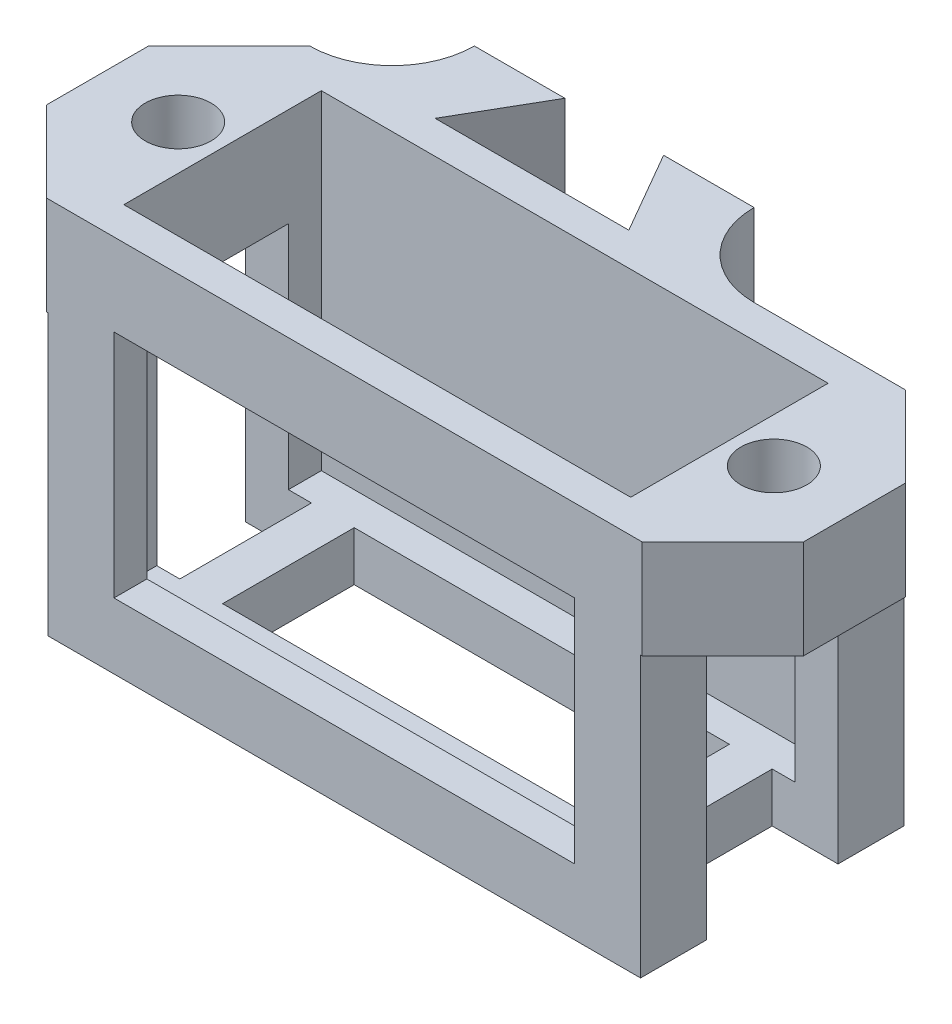
SolidWorks part; units mm, degrees
note: The reader was unsure of these and kept them because the rebuilt part matched: shared geometry of "Sketch3<3>", "Sketch2<3>".
ref_plane "Front Plane" through (0, 0, 0) normal (0, 0, 1) x (1, 0, 0)
ref_plane "Top Plane" through (0, 0, 0) normal (0, 1, 0) x (1, 0, 0)
ref_plane "Right Plane" through (0, 0, 0) normal (1, 0, 0) x (0, 0, -1)
sketch "Sketch1" plane through (0, 0, 0) normal (0, 0, 1) x (1, 0, 0)
  line L0 (-15, 15) -> (15, 15)
  line L1 (15, 15) -> (15, -15)
  line L2 (15, -15) -> (-15, -15)
  line L3 (-15, -15) -> (-15, 15)
  line L4 (-15, 0) -> (15, 0) construction
  line L5 (-15, 5) -> (-23, 5)
  line L6 (-23, 5) -> (-23, -1)
  line L7 (-23, -1) -> (-18, -1)
  line L8 (-18, -1) -> (-18, -18)
  line L9 (-18, -18) -> (18, -18)
  line L10 (18, -18) -> (18, -1)
  line L11 (18, -1) -> (23, -1)
  line L12 (23, -1) -> (23, 5)
  line L13 (23, 5) -> (15, 5)
  line L14 (-15, 5) -> (15, 5)
  point P6 (0, 0)
  dimension "D1" = 30
  dimension "D2" = 30
  dimension "D3" = 20
  dimension "D4" = 3
  dimension "D5" = 3
  dimension "D6" = 5
  dimension "D7" = 6
extrude "Extrude1" add sketch "Sketch1" along normal mid plane 16 contours L12 L13 L1 L2 L3 L5 L6 L7 L8 L9 L10 L11 | L4 L3 L2 L1 | L3 L4 L1 L14
sketch "Sketch2" plane through (0, 0, 0) normal (0, 1, 0) x (1, 0, 0)
  line L0 (-15.4, 0) -> (15.4, 0) construction
  line L1 (0, -6) -> (0, 6) construction
  line L2 (-15.4, -6) -> (-15.4, 6)
  line L3 (-15.4, 6) -> (15.4, 6)
  line L4 (15.4, 6) -> (15.4, -6)
  line L5 (15.4, -6) -> (-15.4, -6)
  line L6 (-18.1, 0) -> (-15.4, 0) construction
  line L7 (15.4, 0) -> (18.1, 0) construction
  line L8 (23, -3.1) -> (18.1, -8)
  line L9 (23, -8) -> (23, 8) construction
  line L11 (23, -8) -> (-23, -8) construction
  line L12 (18.1, -8) -> (23, -8)
  line L14 (23, -8) -> (23, -3.1)
  line L15 (18.1, 8) -> (23, 3.1)
  line L17 (23, 8) -> (-23, 8) construction
  line L18 (23, 3.1) -> (23, 8)
  line L20 (23, 8) -> (18.1, 8)
  line L21 (-18.1, 8) -> (-23, 3.1)
  line L22 (-23, -8) -> (-23, 8) construction
  line L23 (-23, 3.1) -> (-23, 8)
  line L24 (-23, 8) -> (-18.1, 8)
  line L25 (-23, -3.1) -> (-18.1, -8)
  line L26 (-18.1, -8) -> (-23, -8)
  line L27 (-23, -8) -> (-23, -3.1)
  line L28 (-11.4, 4) -> (11.4, 4)
  line L29 (-11.4, 4) -> (-11.4, -4)
  line L30 (-11.4, -4) -> (11.4, -4)
  line L31 (11.4, -4) -> (11.4, 4)
  circle A0 centre (-18.1, 0) radius 2
  circle A1 centre (18.1, 0) radius 2
  point P2 (0, 0)
  point P6 (0, 0)
  point P46 (-11.4, 0)
  point P47 (11.4, 0)
  dimension "D4" = 4
  dimension "D1" = 12
  dimension "D2" = 30.8
  dimension "D3" = 36.2
  dimension "D5" = 2
  dimension "D6" = 4
  dimension "D7" = 4
extrude "Extrude2" cut sketch "Sketch2" against normal blind 20 from surface at 5 contours L27 L26 L25 | A0 | L24 L23 L21 | L30 L31 L28 L29 | L5 L4 L3 L2 L31 L30 L29 L28 | L18 L20 L15 | A1 | L12 L14 L8 starting at face at (0, 5, 0)
sketch "Sketch3" plane through (0, 0, 0) normal (0, 0, 1) x (1, 0, 0)
  line L0 (-14, -14) -> (14, -14)
  line L1 (14, -14) -> (14, 0)
  line L2 (14, 0) -> (-14, 0)
  line L3 (-18, -1) -> (-14, -1)
  line L4 (-14, 0) -> (-14, -14)
  line L5 (-18, -18) -> (18, -18) construction
  line L6 (18, -18) -> (18, -1) construction
  line L7 (-18, -1) -> (-18, -18) construction
  line L8 (-15, 5) -> (15, 5) construction
  line L9 (18, -1) -> (14, -1)
  line L10 (-18, -1) -> (-18, -18) construction
  line L11 (-18, -1) -> (-18, -18)
  line L12 (-18, -18) -> (-14, -18)
  line L13 (-18, -18) -> (18, -18) construction
  line L14 (-14, -18) -> (-14, -14)
  line L17 (18, -1) -> (18, -18)
  line L18 (18, -18) -> (14, -18)
  line L19 (14, -18) -> (14, -14)
  dimension "D1" = 4
  dimension "D2" = 4
  dimension "D3" = 4
  dimension "D4" = 5
extrude "Extrude3" cut sketch "Sketch3" against normal up to surface (14 mm away) from surface at 8 contours L2 L4 L0 L1 up to face at (0, -5, -6) starting at face at (0, -3.75, 8)
extrude "Extrude4" cut sketch "Sketch3<3>" against normal mid plane 8
sketch "Sketch3<3>" plane through (0, 0, 0) normal (0, 0, 1) x (1, 0, 0) same geometry as "Sketch3"
extrude "Extrude5" cut sketch "Sketch2<3>" against normal up to surface (3 mm away) from surface at -15 contours L30 L31 L28 L29 up to face at (0, -18, 0) starting at face at (0, -15, 0)
sketch "Sketch2<3>" plane through (0, 0, 0) normal (0, 1, 0) x (1, 0, 0) same geometry as "Sketch2"
sketch "Sketch4" plane through (0, 0, 0) normal (0, 1, 0) x (1, 0, 0)
  line L0 (3.9, 8) -> (3.9, 13)
  line L1 (3.9, 13) -> (-1.6, 13)
  line L2 (-1.6, 13) -> (1.2868, 8)
  line L3 (18.1, 8) -> (-18.1, 8) construction
  line L4 (-13.1, 8) -> (-13.1, 13)
  line L5 (-13.1, 13) -> (-7.6, 13)
  line L6 (-7.6, 13) -> (-10.4868, 8)
  line L7 (-10.4868, 8) -> (-18.1, 8)
  line L8 (1.2868, 8) -> (8.9, 8)
  line L9 (18.1, 8) -> (-18.1, 8) construction
  line L10 (18.1, 8) -> (-18.1, 8) construction
  arc A0 (-13.1, 13) -> (-18.1, 8) centre (-18.1, 13) cw
  arc A1 (3.9, 13) -> (8.9, 8) centre (8.9, 13) ccw
  dimension "D1" = 5
  dimension "D2" = 17
  dimension "D3" = 6
  dimension "D4" = 60
extrude "Extrude6" add sketch "Sketch4" against normal up to surface (23 mm away) from vertex
